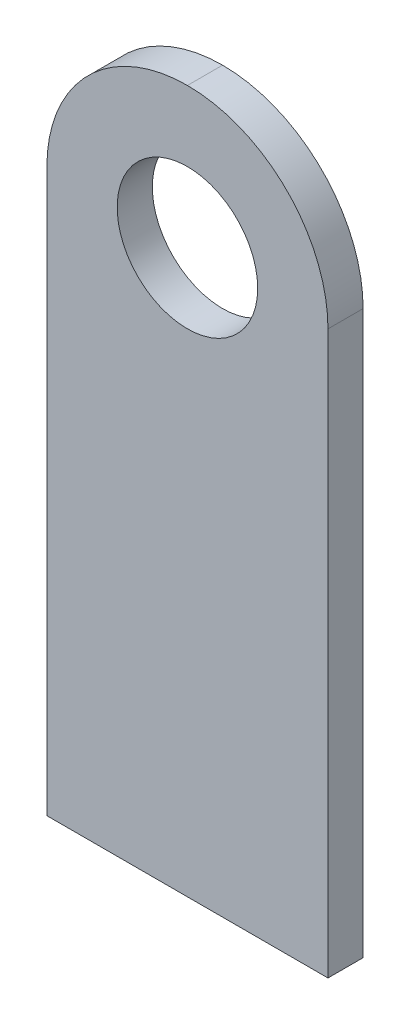
SolidWorks part; units mm, degrees
ref_plane "Front Plane" through (0, 0, 0) normal (0, 0, 1) x (1, 0, 0)
ref_plane "Top Plane" through (0, 0, 0) normal (0, 1, 0) x (1, 0, 0)
ref_plane "Right Plane" through (0, 0, 0) normal (1, 0, 0) x (0, 0, -1)
sketch "Sketch1" plane through (0, 0, 0) normal (0, 1, 0) x (1, 0, 0)
  line L1 (-2, 0.25) -> (2, 0.25)
  line L2 (-2, 0.25) -> (-2, -0.25)
  line L3 (-2, -0.25) -> (2, -0.25)
  line L4 (2, 0.25) -> (2, -0.25)
  line L5 (-2, 0.25) -> (2, -0.25) construction
  line L6 (-2, -0.25) -> (2, 0.25) construction
  point P0 (0, 0)
  dimension "D1" = 0.5
  dimension "D2" = 4
extrude "Boss-Extrude1" add sketch "Sketch1" along normal blind 10
fillet "Fillet1" radius 2 2 edges at (-2, 10, 0) (2, 10, 0)
sketch "Sketch2" plane through (0, 0, 0.25) normal (0, 0, 1) x (1, 0, 0)
  circle A0 centre (0, 8) radius 1
  point P2 (0, 0)
  dimension "D1" = 2
extrude "Cut-Extrude1" cut sketch "Sketch2" against normal up to surface (0.5 mm away) contours A0 up to face at (0, 5.3657, -0.25)
